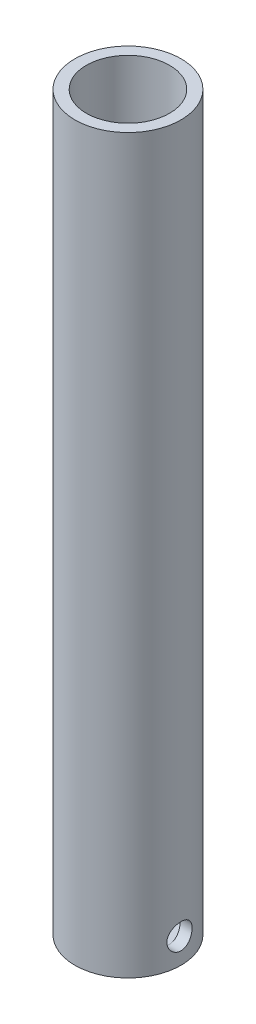
SolidWorks part; units mm, degrees
material "6063-T5"
ref_plane "Front Plane" through (0, 0, 0) normal (0, 0, 1) x (1, 0, 0)
ref_plane "Top Plane" through (0, 0, 0) normal (0, 1, 0) x (1, 0, 0)
ref_plane "Right Plane" through (0, 0, 0) normal (1, 0, 0) x (0, 0, -1)
sketch "Sketch1" plane through (0, 0, 0) normal (0, 1, 0) x (1, 0, 0)
  circle A0 centre (0, 0) radius 10.4648
  circle A1 centre (0, 0) radius 13.335
  dimension "D1" = 20.9296
  dimension "D2" = 26.67
extrude "Boss-Extrude1" add sketch "Sketch1" along normal blind 184.15
extrude "Boss-Extrude2" add sketch "Sketch1<2>" along normal blind 3.175 contours A0
sketch "Sketch1<2>" plane through (0, 0, 0) normal (0, 1, 0) x (1, 0, 0) same geometry as "Sketch1"
ref_plane "Plane1" through (13.335, 0, 0) normal (1, 0, 0) x (0, 0, -1)
sketch "Sketch3" plane through (13.335, 0, 0) normal (1, 0, 0) x (0, 0, -1)
  line L0 (0, -184.15) -> (0, 184.15) construction
  line L1 (13.335, 184.15) -> (-13.335, 184.15) construction
  line L2 (-13.335, 0) -> (13.335, 0) construction
  circle A0 centre (0, 6.35) radius 3.175
  point P0 (0, 6.35)
  point P6 (0, 0)
  dimension "D2" = 6.35
  dimension "D1" = 6.35
extrude "Cut-Extrude1" cut sketch "Sketch3" against normal blind 14.351
